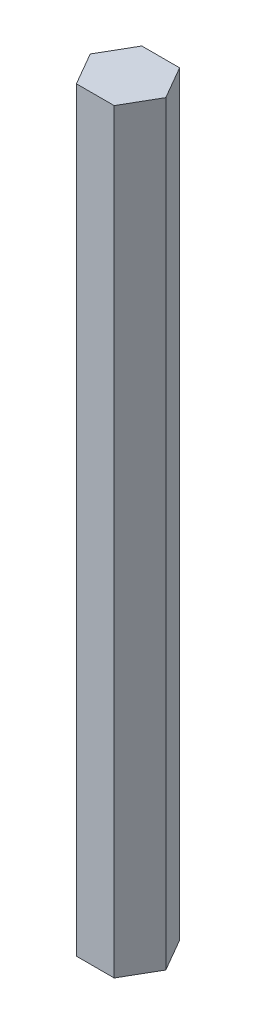
SolidWorks part; units mm, degrees
ref_plane "Front Plane" through (0, 0, 0) normal (0, 0, 1) x (1, 0, 0)
ref_plane "Top Plane" through (0, 0, 0) normal (0, 1, 0) x (1, 0, 0)
ref_plane "Right Plane" through (0, 0, 0) normal (1, 0, 0) x (0, 0, -1)
sketch "Esquisse3" plane through (0, 0, 0) normal (0, 1, 0) x (1, 0, 0)
  line L1 (3, 0) -> (1.5, 2.5981)
  line L2 (1.5, 2.5981) -> (-1.5, 2.5981)
  line L3 (-1.5, 2.5981) -> (-3, 0)
  line L4 (-3, 0) -> (-1.5, -2.5981)
  line L5 (-1.5, -2.5981) -> (1.5, -2.5981)
  line L6 (1.5, -2.5981) -> (3, 0)
  circle A0 centre (0, 0) radius 2.5981 construction
  dimension "D1" = 3
  dimension "D2" = 1.5
extrude "Boss.-Extru.1" add sketch "Esquisse3" along normal blind 60 contours L2 L3 L4 L5 L6 L1
ref_plane "Plan1" through (0, 0, 0) normal (0, 0, 1) x (1, 0, 0)
ref_point "Point1"
ref_axis "Axe1" through (0, 0, 0) along (0, 1, 0)
